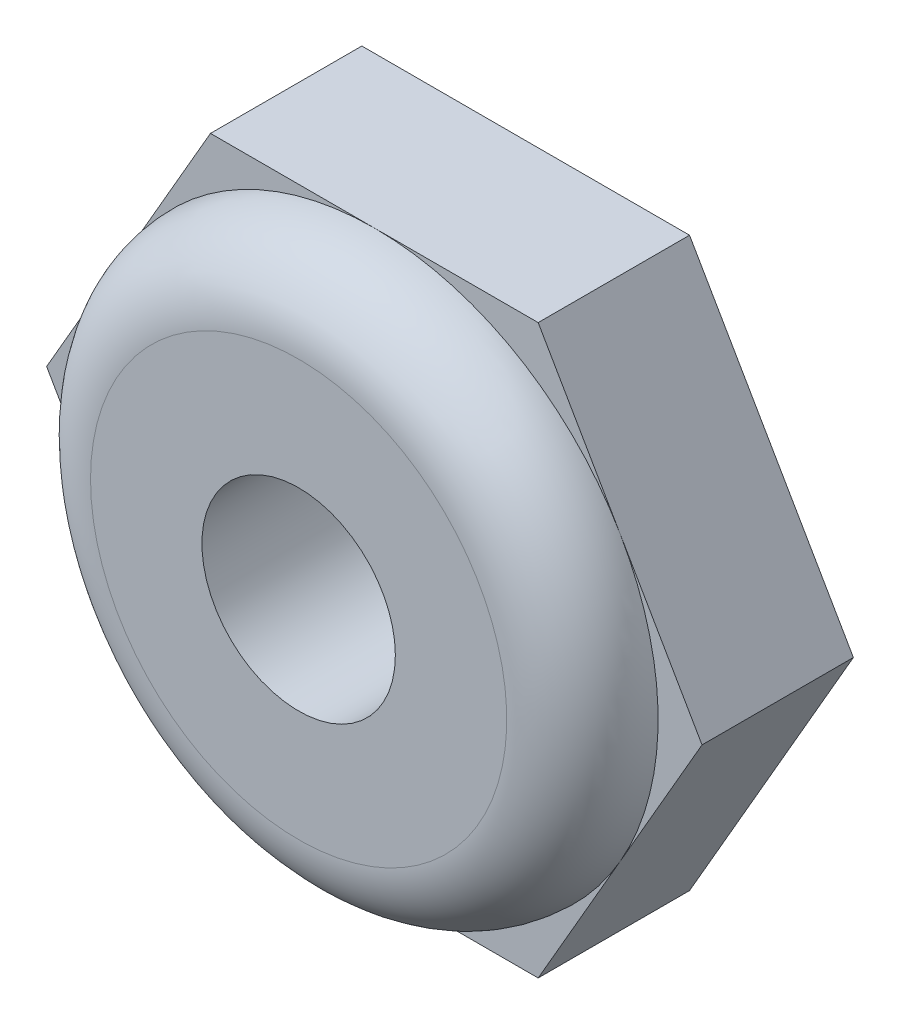
SolidWorks part; units mm, degrees
material "Alloy Steel"
ref_plane "Plane1" through (0, 0, 0) normal (0, 0, 1) x (1, 0, 0)
ref_plane "Plane2" through (0, 0, 0) normal (0, 1, 0) x (1, 0, 0)
ref_plane "Plane3" through (0, 0, 0) normal (1, 0, 0) x (0, 0, -1)
ref_axis "Axis1" through (-83.9706, 0, 0) along (1, 0, 0)
ref_axis "Axis2" through (0, 0, -0.1588) along (0, 0, 1)
ref_axis "Axis3" through (0, 4.3656, 0) along (0, -1, 0)
sketch "Sketch1" plane through (0, 0, 0) normal (0, 0, 1) x (1, 0, 0)
  line L1 (2.2914, 3.9688) -> (-2.2914, 3.9688)
  line L2 (-2.2914, 3.9688) -> (-4.5827, 0)
  line L3 (-4.5827, 0) -> (-2.2914, -3.9688)
  line L4 (-2.2914, -3.9688) -> (2.2914, -3.9687)
  line L5 (2.2914, -3.9687) -> (4.5827, 0)
  line L6 (4.5827, 0) -> (2.2914, 3.9688)
  circle A0 centre (0, 0) radius 3.9688 construction
  circle A1 centre (0, 0) radius 1.3525
  dimension "D1" = 7.9375
  dimension "D2" = 2.7051
extrude "Boss-Extrude1" add sketch "Sketch1" along normal blind 3.175
sketch "Sketch2" plane through (0, 0, 0) normal (1, 0, 0) x (0, 0, -1)
  line L0 (-2.1167, 3.9688) -> (-3.175, 3.9688) construction
  line L1 (-3.175, 3.9688) -> (0, 3.9688) construction
  line L2 (-3.175, 3.9688) -> (-3.175, 2.9104)
  line L3 (-3.175, 0) -> (-3.175, 3.9688) construction
  line L4 (-3.175, 3.9688) -> (-3.175, 5.9531)
  line L5 (-3.175, 5.9531) -> (-2.1167, 5.9531)
  line L6 (-2.1167, 5.9531) -> (-2.1167, 3.9688)
  arc A0 (-3.175, 2.9104) -> (-2.1167, 3.9688) centre (-2.1167, 2.9104) cw
  dimension "D1" = 1.0583
  dimension "D2" = 1.9844
revolve "Cut-Revolve2" cut sketch "Sketch2" angle 360 about axis through (0, 0, -0.1588) along (0, 0, 1)
equation "\"w\"= 0.3125"
equation "\"h\"= 0.125"
equation "\"tap\"= 0.1065"
equation "\"D1@Sketch1\" = \"w\""
equation "\"D2@Sketch1\" = \"tap\""
equation "\"D1@Boss-Extrude1\" = \"h\""
equation "\"D1@Sketch2\" = \"h\" / 3"
equation "\"D2@Sketch2\" = \"w\" / 4"
